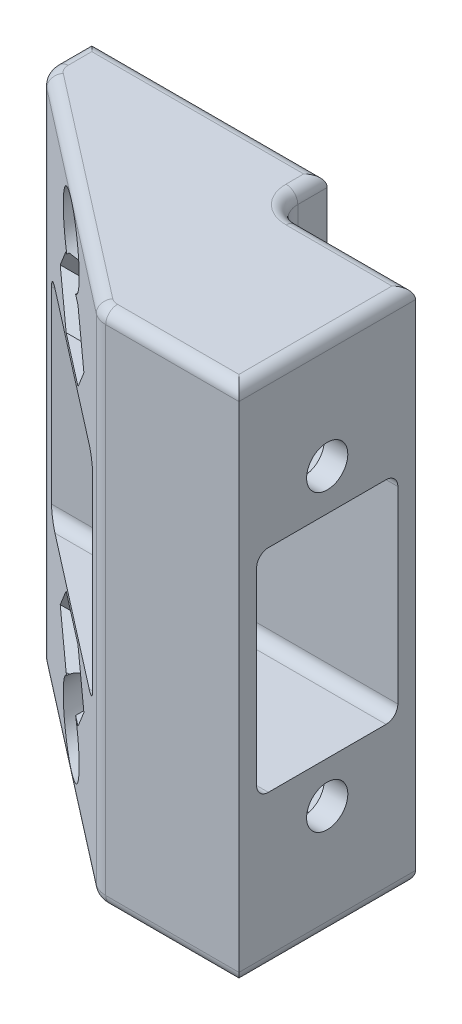
SolidWorks part; units mm, degrees
ref_plane "Top Plane" through (0, 0, 0) normal (0, 0, 1) x (1, 0, 0)
ref_plane "Right Plane" through (0, 0, 0) normal (0, 1, 0) x (1, 0, 0)
ref_plane "Front Plane" through (0, 0, 0) normal (1, 0, 0) x (0, 0, -1)
sketch "Sketch1" plane through (0, 0, 0) normal (0, 1, 0) x (1, 0, 0)
  line L0 (-20, 0) -> (0, 0)
  line L1 (0, 0) -> (0, -4.5)
  line L2 (0, -4.5) -> (12, -4.5)
  line L3 (12, -4.5) -> (12, -19.5)
  line L4 (12, -19.5) -> (0, -19.5)
  line L5 (0, -19.5) -> (-20, -4)
  line L6 (-20, -4) -> (-20, 0)
  point P3 (12, -12)
  dimension "D1" = 15
  dimension "D2" = 12
  dimension "D3" = 12
  dimension "D4" = 4
  dimension "D5" = 20
extrude "Boss-Extrude1" add sketch "Sketch1" along normal mid plane 44
sketch "Sketch2" plane through (12, 0, 0) normal (1, 0, 0) x (0, 0, -1)
  line L0 (-19.5, 0) -> (-4.5, 0) construction
  line L1 (-18.4, 15.5) -> (-5.6, 15.5) construction
  line L2 (-18.4, 15.5) -> (-18.4, -15.5) construction
  line L3 (-18.4, -15.5) -> (-5.6, -15.5) construction
  line L4 (-5.6, 15.5) -> (-5.6, -15.5) construction
  line L5 (-19.5, 22) -> (-19.5, -22) construction
  line L6 (-4.5, 22) -> (-4.5, -22) construction
  line L7 (-18.4, 15.5) -> (-5.6, -15.5) construction
  line L8 (-18, 9) -> (-6, -9) construction
  line L9 (-18, 9) -> (-6, 9)
  line L10 (-18, 9) -> (-18, -9)
  line L11 (-18, -9) -> (-6, -9)
  line L12 (-6, 9) -> (-6, -9)
  circle A0 centre (-12, 12.5) radius 1.75
  circle A1 centre (-12, -12.5) radius 1.75
  point P10 (-12, 0)
  dimension "D3" = 3.5
  dimension "D1" = 31
  dimension "D2" = 12.8
  dimension "D4" = 25
  dimension "D5" = 18
  dimension "D6" = 12
extrude "Cut-Extrude1" cut sketch "Sketch2" against normal through all
sketch "Sketch3" plane through (12, 0, 0) normal (1, 0, 0) x (0, 0, -1)
  line L0 (-24.1892, 0) -> (11.1734, 0) construction
  line L1 (-10.2679, 9.5) -> (-8.5359, 12.5)
  line L2 (-8.5359, 12.5) -> (-10.2679, 15.5)
  line L3 (-10.2679, 15.5) -> (-13.7321, 15.5)
  line L4 (-13.7321, 15.5) -> (-15.4641, 12.5)
  line L5 (-15.4641, 12.5) -> (-13.7321, 9.5)
  line L6 (-13.7321, 9.5) -> (-10.2679, 9.5)
  line L7 (-13.7321, -9.5) -> (-10.2679, -9.5)
  line L8 (-15.4641, -12.5) -> (-13.7321, -9.5)
  line L9 (-13.7321, -15.5) -> (-15.4641, -12.5)
  line L10 (-10.2679, -15.5) -> (-13.7321, -15.5)
  line L11 (-8.5359, -12.5) -> (-10.2679, -15.5)
  line L12 (-10.2679, -9.5) -> (-8.5359, -12.5)
  circle A0 centre (-12, 12.5) radius 3 construction
  circle A1 centre (-12, -12.5) radius 3 construction
  dimension "D1" = 6
extrude "Cut-Extrude2" cut sketch "Sketch3" against normal through all from offset 2 offset against normal yes
sketch "Sketch4" plane through (0, 0, 0) normal (0, 0, -1) x (-1, 0, 0)
  line L0 (10, 22) -> (10, -22) construction
  line L1 (0, 22) -> (20, 22) construction
  line L2 (0, -22) -> (20, -22) construction
  line L3 (0, 0) -> (20, 0) construction
  line L4 (20, 22) -> (20, -22) construction
  circle A0 centre (10, 18) radius 1.75
  circle A1 centre (10, -18) radius 1.75
  dimension "D1" = 3.5
  dimension "D2" = 36
extrude "Cut-Extrude3" cut sketch "Sketch4" against normal through all
sketch "Sketch5" plane through (0, 0, 0) normal (0, 0, -1) x (-1, 0, 0)
  line L0 (-16.9074, 0) -> (30.2234, 0) construction
  circle A1 centre (10, 18) radius 3
  circle A2 centre (10, -18) radius 3
  dimension "D1" = 6
extrude "Cut-Extrude4" cut sketch "Sketch5" against normal through all from offset 2 offset against normal yes
fillet "Fillet1" radius 1 4 edges at (5.0323, 9, 18) (5.0323, -9, 18) (-2.7097, -9, 6) (-2.7097, 9, 6)
fillet "Fillet2" radius 2 1 edges at (0, 0, 4.5)
fillet "Fillet3" radius 2 2 edges at (-20, 0, 4) (0, 0, 19.5)
fillet "Fillet4" radius 1 20 edges at (-10, 22, 0) (0, 22, 1.25) (0.5858, 22, 3.9142) (7, 22, 4.5) (12, 22, 12) (6.3421, 22, 19.5) (0.0368, 22, 19.3923) (-9.883, 22, 11.8407) (-19.7959, 22, 3.8999) (-20, 22, 1.5098) (0.0368, -22, 19.3923) (6.3421, -22, 19.5) (12, -22, 12) (7, -22, 4.5) (0.5858, -22, 3.9142) (0, -22, 1.25) (-10, -22, 0) (-20, -22, 1.5098) (-19.7959, -22, 3.8999) (-9.883, -22, 11.8407)
